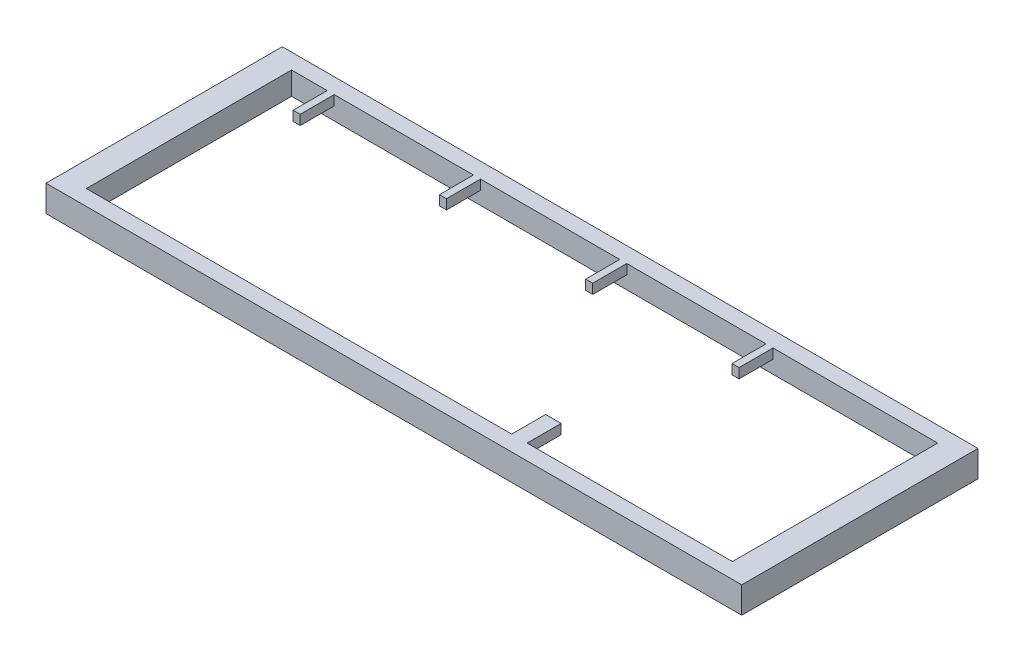
SolidWorks part; units mm, degrees
ref_plane "Front Plane" through (0, 0, 0) normal (0, 0, 1) x (1, 0, 0)
ref_plane "Top Plane" through (0, 0, 0) normal (0, 1, 0) x (1, 0, 0)
ref_plane "Right Plane" through (0, 0, 0) normal (1, 0, 0) x (0, 0, -1)
sketch "Sketch1" plane through (0, 0, 0) normal (0, 1, 0) x (1, 0, 0)
  line L1 (0, 0) -> (390.74, 0)
  line L2 (0, 0) -> (0, 132.7)
  line L3 (0, 132.7) -> (390.74, 132.7)
  line L4 (390.74, 0) -> (390.74, 132.7)
  line L5 (13.92, 124) -> (376.82, 124)
  line L6 (13.92, 124) -> (13.92, 8.7)
  line L7 (13.92, 8.7) -> (376.82, 8.7)
  line L8 (376.82, 124) -> (376.82, 8.7)
  point P9 (195.37, 124)
  point P10 (195.37, 132.7)
  point P11 (13.92, 66.35)
  point P12 (0, 66.35)
  dimension "D1" = 362.9
  dimension "D2" = 115.3
  dimension "D3" = 8.7
  dimension "D4" = 13.92
extrude "Main Body" add sketch "Sketch1" along normal blind 14.8
sketch "Sketch2" plane through (0, 0, 0) normal (0, -1, 0) x (1, 0, 0)
  line L0 (390.74, -132.7) -> (0, -132.7) construction
  line L1 (388.74, -130.7) -> (2, -130.7)
  line L2 (388.74, -130.7) -> (388.74, -2)
  line L3 (388.74, -2) -> (2, -2)
  line L4 (2, -130.7) -> (2, -2)
  line L5 (390.74, 0) -> (390.74, -132.7) construction
  point P4 (195.37, -130.7)
  point P7 (195.37, -132.7)
  point P8 (388.74, -66.35)
  point P11 (390.74, -66.35)
  dimension "D1" = 2
  dimension "D2" = 2
extrude "Alignment Guide" cut sketch "Sketch2" against normal blind 2 contours L2 L1 L4 L3
sketch "Sketch3" plane through (0, 14.8, 0) normal (0, 1, 0) x (1, 0, 0)
  line L0 (13.92, 8.7) -> (376.82, 8.7) construction
  line L1 (252.82, 27.8) -> (261.52, 27.8)
  line L2 (252.82, 27.8) -> (252.82, 8.7)
  line L3 (252.82, 8.7) -> (261.52, 8.7)
  line L4 (261.52, 27.8) -> (261.52, 8.7)
  line L5 (376.82, 8.7) -> (376.82, 124) construction
  line L6 (376.82, 124) -> (13.92, 124) construction
  line L7 (33.92, 124) -> (37.87, 124)
  line L8 (33.92, 124) -> (33.92, 104.9)
  line L9 (33.92, 104.9) -> (37.87, 104.9)
  line L10 (37.87, 124) -> (37.87, 104.9)
  line L11 (13.92, 124) -> (13.92, 8.7) construction
  line L12 (116.07, 124) -> (120.02, 124)
  line L13 (116.07, 124) -> (116.07, 104.9)
  line L14 (116.07, 104.9) -> (120.02, 104.9)
  line L15 (120.02, 124) -> (120.02, 104.9)
  line L16 (198.22, 124) -> (202.17, 124)
  line L17 (198.22, 124) -> (198.22, 104.9)
  line L18 (198.22, 104.9) -> (202.17, 104.9)
  line L19 (202.17, 124) -> (202.17, 104.9)
  line L20 (280.37, 124) -> (284.32, 124)
  line L21 (280.37, 124) -> (280.37, 104.9)
  line L22 (280.37, 104.9) -> (284.32, 104.9)
  line L23 (284.32, 124) -> (284.32, 104.9)
  point P8 (257.17, 8.7)
  dimension "D1" = 115.3
  dimension "D2" = 124
  dimension "D3" = 19.1
  dimension "D4" = 3.95
  dimension "D5" = 19.1
  dimension "D6" = 78.2
  dimension "D7" = 78.2
  dimension "D8" = 78.2
  dimension "D9" = 20
extrude "Blockers" add sketch "Sketch3" against normal blind 5.5
